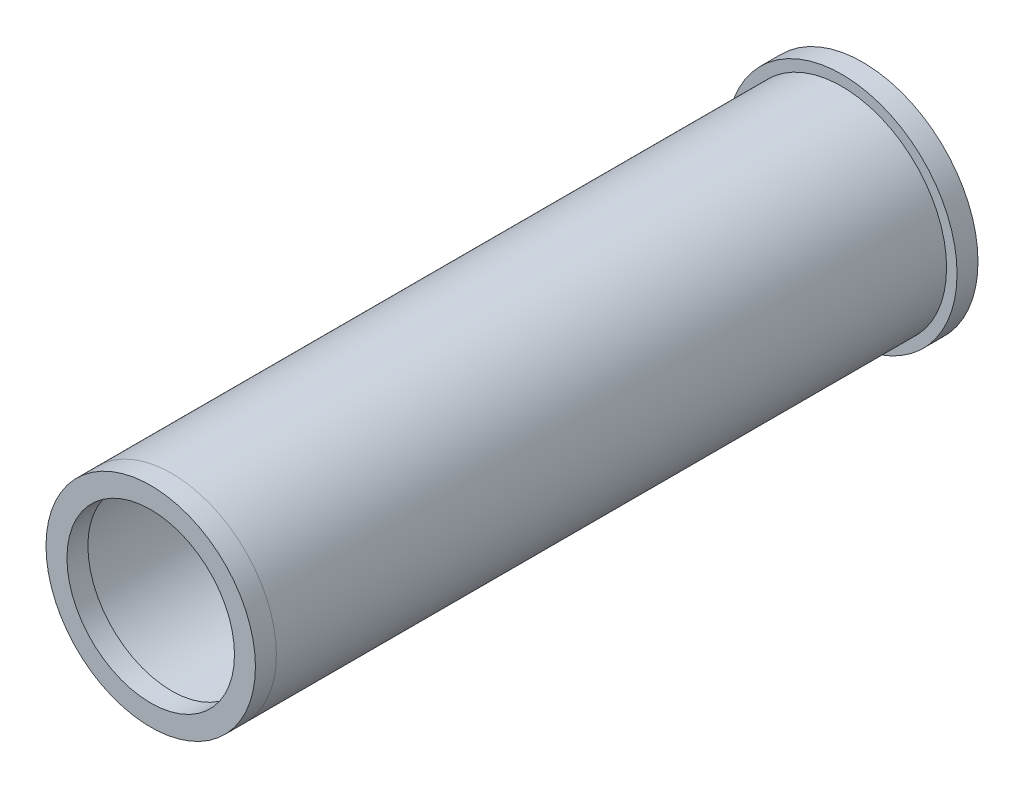
SolidWorks part; units mm, degrees
ref_plane "Front Plane" through (0, 0, 0) normal (0, 0, 1) x (1, 0, 0)
ref_plane "Top Plane" through (0, 0, 0) normal (0, 1, 0) x (1, 0, 0)
ref_plane "Right Plane" through (0, 0, 0) normal (1, 0, 0) x (0, 0, -1)
sketch "Sketch1" plane through (0, 0, 0) normal (0, 0, 1) x (1, 0, 0)
  circle A0 centre (0, 0) radius 57.15
  circle A1 centre (0, 0) radius 63.5
  circle A2 centre (0, 0) radius 69.85
  dimension "D1" = 139.7
  dimension "D2" = 127
  dimension "D3" = 114.3
extrude "Boss-Extrude1" add sketch "Sketch1" against normal blind 12.7 contours A2 A1 | A1 A0 region at (-61.7039, 0, 0) region at (-67.8743, 0, 0)
extrude "Boss-Extrude2" add sketch "Sketch1<3>" along normal blind 406.4 contours A1 A0 region at (-61.7039, 0, 0)
sketch "Sketch1<3>" plane through (0, 0, 0) normal (0, 0, 1) x (1, 0, 0) same geometry as "Sketch1"
sketch "Sketch2" plane through (0, 0, 406.4) normal (0, 0, 1) x (1, 0, 0)
  circle A0 centre (0, 0) radius 50.8
  circle A3 centre (0, 0) radius 63.5 construction
  circle A4 centre (0, 0) radius 63.5
  dimension "D1" = 101.6
extrude "Boss-Extrude3" add sketch "Sketch2" along normal blind 12.7 separate body
